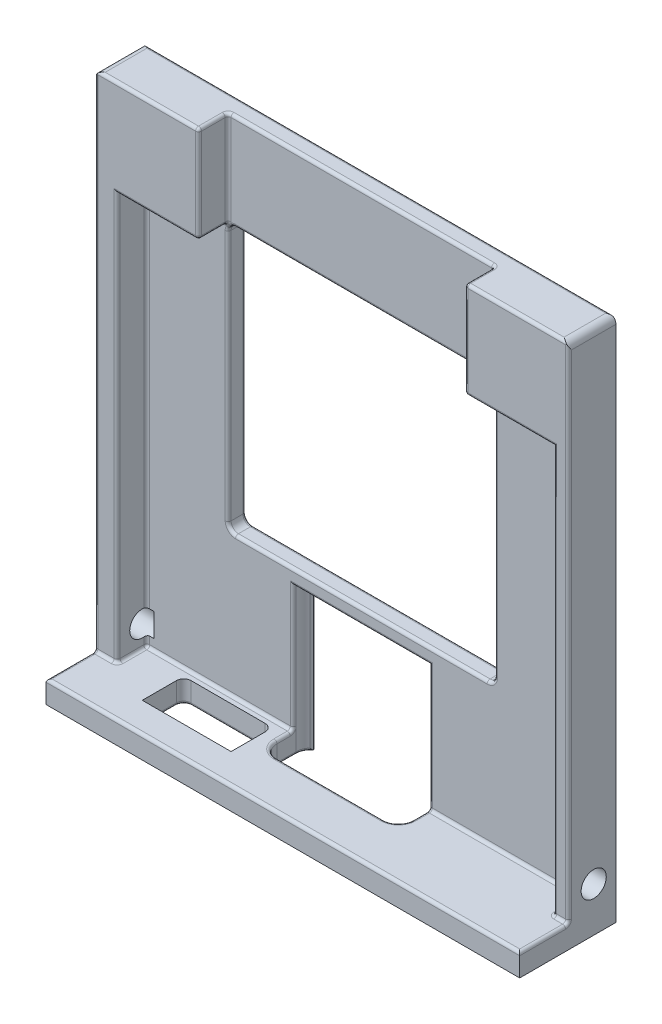
SolidWorks part; units mm, degrees
ref_plane "前视基准面" through (0, 0, 0) normal (0, 0, 1) x (1, 0, 0)
ref_plane "上视基准面" through (0, 0, 0) normal (0, 1, 0) x (1, 0, 0)
ref_plane "右视基准面" through (0, 0, 0) normal (1, 0, 0) x (0, 0, -1)
sketch "草图1" plane through (0, 0, 0) normal (0, 0, 1) x (1, 0, 0)
  line L0 (0, 0) -> (16, 0)
  line L1 (16, 0) -> (16, 35.5)
  line L2 (16, 35.5) -> (-16, 35.5)
  line L3 (-16, 35.5) -> (-16, 0)
  line L4 (-16, 0) -> (0, 0)
  dimension "D1" = 32
  dimension "D2" = 35.5
extrude "凸台-拉伸1" add sketch "草图1" along normal blind 6.5
sketch "草图2" plane through (0, 0, 6.5) normal (0, 0, 1) x (1, 0, 0)
  line L6 (-16, 1.5) -> (16, 1.5)
  line L8 (16, 0) -> (16, 35.5) construction
  line L9 (16, 1.5) -> (16, 35.5)
  line L10 (16, 35.5) -> (-16, 35.5)
  line L11 (-16, 35.5) -> (-16, 1.5)
  line L12 (-16, 35.5) -> (-16, 0) construction
  line L14 (-16, 0) -> (16, 0) construction
  dimension "D1" = 1.5
extrude "切除-拉伸2" cut sketch "草图2" against normal blind 3.3
sketch "草图3" plane through (0, 0, 0) normal (0, -1, 0) x (-1, 0, 0)
  line L3 (11.5, -4.5) -> (5.5, -4.5)
  line L8 (11.5, -4.5) -> (11.5, -1.7)
  line L9 (11.5, -1.7) -> (5.5, -1.7)
  line L10 (5.5, -1.7) -> (5.5, -4.5)
  dimension "D3" = 2.8
  dimension "D4" = 6
extrude "切除-拉伸3" cut sketch "草图3" against normal blind 2.2
sketch "草图4" plane through (0, 0, 3.2) normal (0, 0, 1) x (1, 0, 0)
  line L0 (-14.5, 1.5) -> (15, 1.5)
  line L1 (-16, 1.5) -> (-11.5, 1.5) construction
  line L2 (-14.5, 1.5) -> (-14.5, 29)
  line L4 (15, 29) -> (15, 1.5)
  line L5 (-5.5, 1.5) -> (16, 1.5) construction
  line L6 (16, 1.5) -> (16, 35.5) construction
  line L7 (-14.5, 29) -> (-9, 29)
  line L11 (9, 29) -> (15, 29)
  line L12 (-9, 29) -> (-9, 35.5)
  line L13 (16, 35.5) -> (-16, 35.5) construction
  line L14 (-9, 35.5) -> (9, 35.5)
  line L15 (9, 35.5) -> (9, 29)
  dimension "D1" = 1
  dimension "D2" = 27.5
  dimension "D3" = 29.5
  dimension "D4" = 18
extrude "切除-拉伸4" cut sketch "草图4" against normal blind 2
sketch "草图5" plane through (0, 0, 0) normal (0, -1, 0) x (1, 0, 0)
  line L3 (4.6, 2.3) -> (4.6, 1)
  line L4 (-16, 0) -> (16, 0) construction
  line L6 (-4.6, 1) -> (-4.6, 2.3)
  line L8 (-3.6, 3.3) -> (3.6, 3.3)
  line L9 (3.6, 0) -> (0, 0)
  line L10 (0, 0) -> (-3.6, 0)
  arc A0 (3.6, 3.3) -> (4.6, 2.3) centre (3.6, 2.3) cw
  arc A1 (4.6, 1) -> (3.6, 0) centre (3.6, 1) cw
  arc A2 (-3.6, 0) -> (-4.6, 1) centre (-3.6, 1) cw
  arc A3 (-4.6, 2.3) -> (-3.6, 3.3) centre (-3.6, 2.3) cw
  point P3 (4.6, 3.3)
  point P13 (4.6, 0)
  point P16 (-4.6, 0)
  point P19 (-4.6, 3.3)
  dimension "D3" = 1
  dimension "D1" = 9.2
  dimension "D2" = 3.3
extrude "切除-拉伸5" cut sketch "草图5" against normal blind 10
sketch "草图6" plane through (0, 0, 1.2) normal (0, 0, 1) x (1, 0, 0)
  line L2 (0, 11) -> (9, 11)
  line L3 (9, 11) -> (9, 29)
  line L4 (9, 29) -> (-9, 29)
  line L5 (-9, 29) -> (-9, 11)
  line L6 (-9, 11) -> (0, 11)
  dimension "D2" = 18
  dimension "D3" = 18
extrude "切除-拉伸6" cut sketch "草图6" against normal blind 2
fillet "圆角3" radius 0.2 2 edges at (-3.6, 5, 0) (3.6, 5, 0)
fillet "圆角4" radius 0.5 2 edges at (-5.5, 0.75, 1.7) (-11.5, 0.75, 1.7)
fillet "圆角10" radius 0.2 1 edges at (0, 35.5, 0)
fillet "圆角14" radius 0.2 16 edges at (16, 1.5, 4.85) (15, 1.5, 2.2) (-16, 1.5, 4.85) (-14.5, 1.5, 2.2) (12.5, 35.5, 3.2) (16, 18.5, 3.2) (15.5, 1.5, 3.2) (15, 15.25, 3.2) (12, 29, 3.2) (9, 32.25, 3.2) (-15.25, 1.5, 3.2) (-16, 18.5, 3.2) (-12.5, 35.5, 3.2) (-9, 32.25, 3.2) (-11.75, 29, 3.2) (-14.5, 15.25, 3.2)
fillet "圆角17" radius 0.2 4 edges at (9.0586, 29.0586, 3.1414) (-9.0586, 29.0586, 3.1414) (9, 29, 2.1) (-9, 29, 2.1)
fillet "圆角18" radius 0.2 25 edges at (-14.5, 15.35, 1.2) (-14.4414, 1.5586, 1.2) (15, 15.35, 1.2) (14.9414, 1.5586, 1.2) (-9.45, 1.5, 1.2) (9.7, 1.5, 1.2) (0, 1.5, 3.3) (4.3071, 1.5, 3.0071) (-4.3071, 1.5, 3.0071) (-9.0586, 35.4414, 3.1414) (9.0586, 35.4414, 3.1414) (4.6, 1.5, 1.75) (-4.6, 1.5, 1.75) (-9, 35.5, 2.1) (9, 35.5, 2.1) (4.6, 5.75, 1.2) (0, 10, 1.2) (-4.6, 5.75, 1.2) (-11.85, 29, 1.2) (-9.0586, 29.0586, 1.2) (-9, 32.35, 1.2) (0, 35.5, 1.2) (9, 32.35, 1.2) (9.0586, 29.0586, 1.2) (12.1, 29, 1.2)
fillet "圆角19" radius 0.5 4 edges at (-9, 11, 0.6) (9, 11, 0.6) (-9, 29, 0.619) (9, 29, 0.619)
fillet "圆角20" radius 0.2 8 edges at (-8.8536, 11.1464, 1.2) (0, 11, 1.2) (8.8536, 11.1464, 1.2) (9, 20, 1.2) (8.8536, 28.8536, 1.2) (0, 29, 1.2) (-8.8536, 28.8536, 1.2) (-9, 20, 1.2)
fillet "圆角21" radius 0.2 13 edges at (-11.3536, 0, 1.8464) (-11.5, 0, 3.35) (-8.5, 0, 1.7) (-5.6464, 0, 1.8464) (-5.5, 0, 3.35) (-8.5, 0, 4.5) (4.5342, 0, 0.6432) (4.6, 0, 1.65) (4.3071, 0, 3.0071) (0, 0, 3.3) (-4.3071, 0, 3.0071) (-4.5342, 0, 0.6432) (-4.6, 0, 1.65)
fillet "圆角23" radius 0.5 2 edges at (16, 35.5, 1.6) (-16, 35.5, 1.6)
sketch "草图8" plane through (0, 0, 0) normal (0, 0, -1) x (-1, 0, 0)
  circle A0 centre (-12.9, 32.3) radius 1.55
  circle A1 centre (12.9, 32.3) radius 1.55
extrude "切除-拉伸8" cut sketch "草图8" against normal blind 2.2
fillet "圆角25" radius 0.2 10 edges at (-8.8536, 11.1464, 0) (-9, 20, 0) (-8.8536, 28.8536, 0) (0, 29, 0) (8.8536, 28.8536, 0) (9, 20, 0) (8.8536, 11.1464, 0) (0, 11, 0) (11.35, 32.3, 0) (-14.45, 32.3, 0)
fillet "圆角26" radius 0.2 1 edges at (0, 1.5, 6.5)
sketch "草图9" plane through (-16, 0, 0) normal (-1, 0, 0) x (0, 0, 1)
  circle A0 centre (1.5, 3) radius 0.85
extrude "切除-拉伸9" cut sketch "草图9" against normal blind 2
sketch "草图10" plane through (16, 0, 0) normal (1, 0, 0) x (0, 0, -1)
  circle A0 centre (-1.5, 3) radius 0.85
extrude "切除-拉伸10" cut sketch "草图10" against normal blind 2
